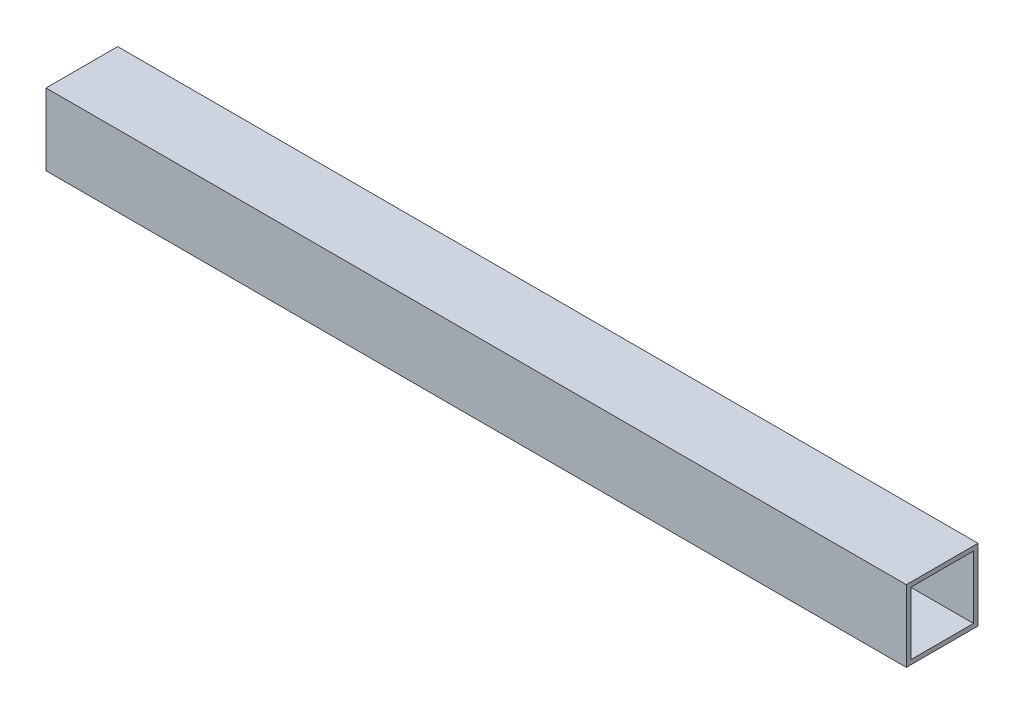
SolidWorks part; units mm, degrees
material "6061-T6 (SS)"
ref_plane "Front" through (0, 0, 0) normal (0, 0, 1) x (1, 0, 0)
ref_plane "Top" through (0, 0, 0) normal (0, 1, 0) x (1, 0, 0)
ref_plane "Right" through (0, 0, 0) normal (1, 0, 0) x (0, 0, -1)
sketch "Sketch1" plane through (0, 0, 0) normal (1, 0, 0) x (0, 0, -1)
  line L1 (12.7, -12.7) -> (-12.7, -12.7)
  line L2 (12.7, -12.7) -> (12.7, 12.7)
  line L3 (12.7, 12.7) -> (-12.7, 12.7)
  line L4 (-12.7, -12.7) -> (-12.7, 12.7)
  line L5 (12.7, -12.7) -> (-12.7, 12.7) construction
  line L6 (12.7, 12.7) -> (-12.7, -12.7) construction
  point P0 (0, 0)
  dimension "D1" = 25.4
extrude "Extrude-Thin1" add sketch "Sketch1" along normal up to surface (304.8 mm away) thin thin type one direction reverse wall 1.5875
